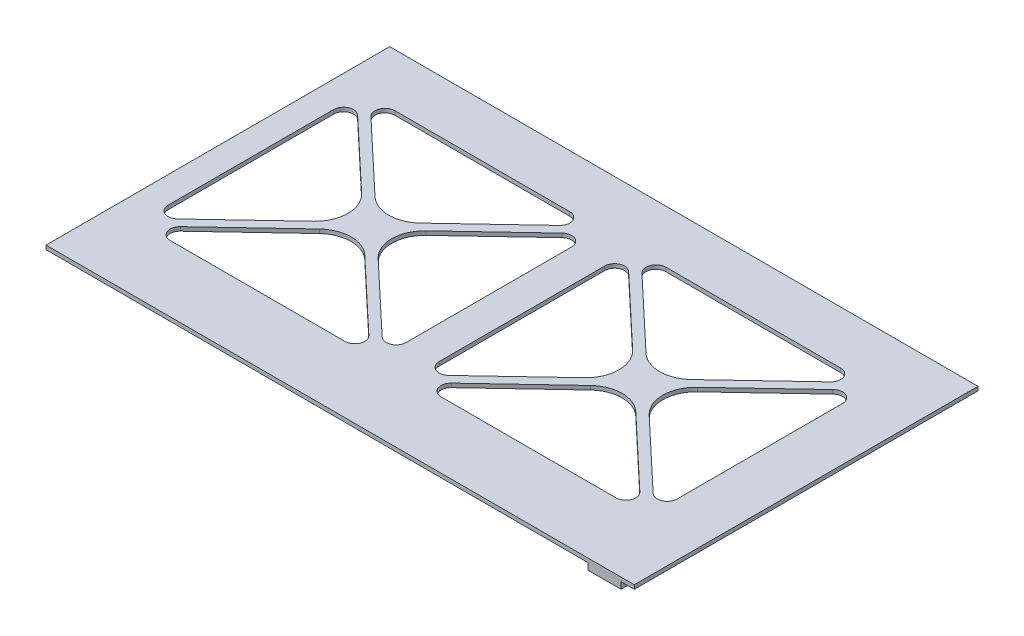
SolidWorks part; units mm, degrees
ref_plane "Front Plane" through (0, 0, 0) normal (0, 0, 1) x (1, 0, 0)
ref_plane "Top Plane" through (0, 0, 0) normal (0, 1, 0) x (1, 0, 0)
ref_plane "Right Plane" through (0, 0, 0) normal (1, 0, 0) x (0, 0, -1)
sketch "Sketch1" plane through (0, 0, 0) normal (0, 1, 0) x (1, 0, 0)
  line L0 (90, 88) -> (162, 88)
  line L1 (0, 0) -> (178, 0)
  line L2 (0, 0) -> (0, 104)
  line L3 (0, 104) -> (178, 104)
  line L4 (178, 0) -> (178, 104)
  line L5 (8, 88) -> (80, 88)
  line L6 (8, 88) -> (8, 20)
  line L7 (8, 20) -> (80, 20)
  line L8 (162, 88) -> (162, 20)
  line L10 (80, 88) -> (80, 20)
  line L12 (90, 88) -> (90, 20)
  line L13 (90, 20) -> (162, 20)
  dimension "D1" = 178
  dimension "D2" = 104
  dimension "D3" = 16
  dimension "D4" = 16
  dimension "D5" = 8
  dimension "D6" = 20
  dimension "D7" = 10
  dimension "D8" = 72
extrude "Boss-Extrude1" add sketch "Sketch1" along normal blind 1.2
sketch "Sketch2" plane through (0, 0, -104) normal (0, 0, -1) x (-1, 0, 0)
  line L0 (-178, 0) -> (0, 0) construction
  line L1 (-151, 0) -> (-148, 0)
  line L2 (-151, 0) -> (-151, -4)
  line L3 (-151, -4) -> (-148, -4)
  line L4 (-148, 0) -> (-148, -2)
  line L5 (-178, 1.2) -> (-178, 0) construction
  line L6 (-148, -4) -> (-144, -4)
  line L7 (-144, 0) -> (-141, 0)
  line L8 (-144, 0) -> (-144, -2)
  line L9 (-144, -4) -> (-141, -4)
  line L10 (-141, 0) -> (-141, -4)
  line L13 (-148, -2) -> (-144, -2)
  dimension "D1" = 27
  dimension "D2" = 3
  dimension "D3" = 4
  dimension "D4" = 4
  dimension "D5" = 3
  dimension "D6" = 4
  dimension "D7" = 3
  dimension "D8" = 3
extrude "Boss-Extrude2" add sketch "Sketch2" against normal blind 5
ref_plane "Plane1" through (78.75, 0, 0) normal (-1, 0, 0) x (0, 0, 1)
mirror "Mirror1" about plane through (78.75, 0, 0) normal (-1, 0, 0) of "Boss-Extrude2"
sketch "Sketch3" plane through (0, 0, 0) normal (0, -1, 0) x (1, 0, 0)
  line L0 (0, 0) -> (178, 0) construction
  line L1 (10, -5.2) -> (122, -5.2)
  line L2 (10, -5.2) -> (10, -15.2)
  line L3 (10, -15.2) -> (122, -15.2)
  line L4 (122, -5.2) -> (122, -15.2)
  line L5 (178, 0) -> (178, -104) construction
  line L6 (0, -104) -> (0, 0) construction
  dimension "D1" = 10
  dimension "D2" = 5.2
  dimension "D3" = 56
  dimension "D4" = 10
extrude "Boss-Extrude3" add sketch "Sketch3" along normal blind 0.8
sketch "Sketch4" plane through (0, 0, 0) normal (0, -1, 0) x (1, 0, 0)
  line L0 (0, -104) -> (0, 0) construction
  line L1 (10, -5.2) -> (0, -5.2)
  line L2 (10, -5.2) -> (10, -15.2)
  line L3 (10, -15.2) -> (0, -15.2)
  line L4 (0, -5.2) -> (0, -15.2)
extrude "Boss-Extrude4" add sketch "Sketch4" along normal blind 2.8
sketch "Sketch5" plane through (0, 0, 0) normal (-1, 0, 0) x (0, 0, 1)
  line L1 (-7.2, 0) -> (-13.2, 0)
  line L2 (-7.2, 0) -> (-7.2, -2)
  line L3 (-7.2, -2) -> (-13.2, -2)
  line L4 (-13.2, 0) -> (-13.2, -2)
  line L6 (-5.2, -2.8) -> (-5.2, 0) construction
  line L7 (-15.2, -2.8) -> (-15.2, 0) construction
  point P7 (0, 0)
  point P8 (0, 0)
  point P9 (0, 0)
  point P10 (0, 0)
  point P11 (0, 0)
  dimension "D1" = 2
  dimension "D2" = 2
  dimension "D3" = 2
extrude "Cut-Extrude1" cut sketch "Sketch5" against normal blind 10
sketch "Sketch6" plane through (0, 0, -104) normal (0, 0, -1) x (-1, 0, 0)
  line L0 (0, 0) -> (-122, 0) construction
  line L1 (-94.25, 0) -> (-84.25, 0)
  line L2 (-94.25, 0) -> (-94.25, -7.8)
  line L3 (-94.25, -7.8) -> (-84.25, -7.8)
  line L4 (-84.25, 0) -> (-84.25, -7.8)
  line L6 (0, 1.2) -> (0, 0) construction
  dimension "D1" = 84.25
  dimension "D2" = 10
  dimension "D3" = 7.8
extrude "Boss-Extrude5" add sketch "Sketch6" against normal blind 6
sketch "Sketch7" plane through (0, 0, -104) normal (0, 0, -1) x (-1, 0, 0)
  line L0 (-94.25, -7.8) -> (-84.25, -7.8) construction
  line L1 (-84.25, -7.8) -> (-84.25, 0) construction
  circle A0 centre (-89.25, -3.3) radius 1.5
  dimension "D1" = 3
  dimension "D2" = 4.5
  dimension "D3" = 5
fillet "Fillet1" radius 10 2 edges at (94.25, 0, -101) (84.25, 0, -101)
fillet "Fillet2" radius 6 2 edges at (94.25, -7.8, -101) (84.25, -7.8, -101)
extrude "Cut-Extrude2" cut sketch "Sketch7" against normal blind 4
fillet "Fillet3" radius 3 5 edges at (99.0679, -1.3037, -98) (93.2283, -7.0178, -98) (79.4321, -1.3037, -98) (85.2717, -7.0178, -98) (89.25, -7.8, -98)
sketch "Sketch8" plane through (0, 0, 0) normal (0, -1, 0) x (1, 0, 0)
  line L0 (10, -15.2) -> (122, -15.2) construction
  line L1 (122, -5.2) -> (125, -5.2)
  line L2 (122, -5.2) -> (122, -15.2)
  line L3 (122, -15.2) -> (125, -15.2)
  line L4 (125, -5.2) -> (125, -15.2)
  dimension "D1" = 0
  dimension "D2" = 3
extrude "Boss-Extrude6" add sketch "Sketch8" along normal blind 2.8
fillet "Fillet4" radius 3 1 edges at (125, 0, -10.2)
sketch "Sketch9" plane through (0, 0, 0) normal (0, -1, 0) x (1, 0, 0)
  line L0 (178, 0) -> (178, -104) construction
  line L1 (164, 0) -> (174, 0)
  line L2 (164, 0) -> (164, -78)
  line L3 (164, -78) -> (174, -78)
  line L4 (174, 0) -> (174, -78)
  line L5 (0, 0) -> (178, 0) construction
  dimension "D1" = 78
  dimension "D2" = 10
  dimension "D3" = 4
  dimension "D4" = 0
extrude "Boss-Extrude7" add sketch "Sketch9" along normal blind 2
sketch "Sketch10" plane through (0, 1.2, 0) normal (0, 1, 0) x (1, 0, 0)
  line L0 (15.4969, 82.8172) -> (37.1399, 62.411)
  line L1 (80, 88) -> (8, 88) construction
  line L2 (80, 20) -> (80, 88) construction
  line L3 (80, 28.9518) -> (80, 51.7573)
  line L4 (80, 51.7573) -> (83.6075, 51.7573)
  line L5 (83.6075, 51.7573) -> (83.6075, 17.0328)
  line L6 (83.6075, 17.0328) -> (48.4744, 17.0328)
  line L7 (48.4744, 17.0328) -> (48.4744, 20)
  line L8 (8, 20) -> (80, 20) construction
  line L9 (48.4744, 20) -> (70.4451, 20)
  line L10 (72.5031, 25.1828) -> (50.8601, 45.589)
  line L11 (8, 88) -> (8, 20) construction
  line L12 (8, 79.0482) -> (8, 56.3328)
  line L13 (8, 56.3328) -> (3.4551, 56.3328)
  line L14 (3.4551, 56.3328) -> (3.4551, 92.7731)
  line L15 (3.4551, 92.7731) -> (41.5295, 92.7731)
  line L16 (41.5295, 92.7731) -> (41.5295, 88)
  line L17 (41.5295, 88) -> (17.5549, 88)
  line L18 (72.5031, 82.8172) -> (50.8601, 62.411)
  line L19 (8, 28.9518) -> (8, 51.7573)
  line L20 (8, 51.7573) -> (3.4551, 51.7573)
  line L21 (3.4551, 51.7573) -> (3.4551, 17.0328)
  line L22 (3.4551, 17.0328) -> (45.0166, 17.0328)
  line L23 (45.0166, 17.0328) -> (45.0166, 20)
  line L24 (45.0166, 20) -> (17.5549, 20)
  line L25 (15.4969, 25.1828) -> (37.1399, 45.589)
  line L26 (80, 79.0482) -> (80, 57.5004)
  line L27 (80, 57.5004) -> (83.6075, 57.5004)
  line L28 (83.6075, 57.5004) -> (83.6075, 92.7731)
  line L29 (83.6075, 92.7731) -> (53.7555, 92.7731)
  line L30 (53.7555, 92.7731) -> (53.7555, 88)
  line L31 (53.7555, 88) -> (70.4451, 88)
  line L32 (34.2225, 46.7241) -> (13.058, 26.769)
  line L33 (53.7775, 61.2759) -> (74.942, 81.231)
  line L34 (53.7775, 46.7241) -> (74.942, 26.769)
  line L35 (34.2225, 61.2759) -> (13.058, 81.231)
  arc A0 (74.942, 26.769) -> (80, 28.9518) centre (77, 28.9518) ccw
  arc A1 (70.4451, 20) -> (72.5031, 25.1828) centre (70.4451, 23) ccw
  arc A2 (17.5549, 20) -> (15.4969, 25.1828) centre (17.5549, 23) cw
  arc A3 (13.058, 26.769) -> (8, 28.9518) centre (11, 28.9518) cw
  arc A4 (13.058, 81.231) -> (8, 79.0482) centre (11, 79.0482) ccw
  arc A5 (15.4969, 82.8172) -> (17.5549, 88) centre (17.5549, 85) cw
  arc A6 (72.5031, 82.8172) -> (70.4451, 88) centre (70.4451, 85) ccw
  arc A7 (74.942, 81.231) -> (80, 79.0482) centre (77, 79.0482) cw
  arc A8 (50.8601, 62.411) -> (37.1399, 62.411) centre (44, 69.6869) cw
  arc A9 (37.1399, 45.589) -> (50.8601, 45.589) centre (44, 38.3131) cw
  arc A10 (53.7775, 61.2759) -> (53.7775, 46.7241) centre (60.6376, 54) ccw
  arc A11 (34.2225, 46.7241) -> (34.2225, 61.2759) centre (27.3624, 54) ccw
  point P46 (80, 22)
  point P49 (78, 20)
  point P52 (10, 20)
  point P55 (8, 22)
  point P58 (8, 86)
  point P61 (10, 88)
  point P64 (78, 88)
  point P67 (80, 86)
  point P74 (46.0606, 54)
  point P77 (41.9394, 54)
  dimension "D15" = 3
  dimension "D16" = 10
  dimension "D1" = 4.7731
  dimension "D2" = 3.6075
  dimension "D3" = 3.6075
  dimension "D4" = 2.9672
  dimension "D5" = 4.5449
  dimension "D6" = 4.5449
  dimension "D7" = 2
  dimension "D8" = 2
  dimension "D9" = 2
  dimension "D10" = 2
  dimension "D11" = 2
  dimension "D12" = 2
  dimension "D13" = 2
  dimension "D14" = 2
extrude "Boss-Extrude8" add sketch "Sketch10" against normal blind 1.2
ref_plane "Plane2" through (85, 0, 0) normal (1, 0, 0) x (0, 0, -1)
mirror "Mirror2" about plane through (85, 0, 0) normal (1, 0, 0) of "Boss-Extrude8"
